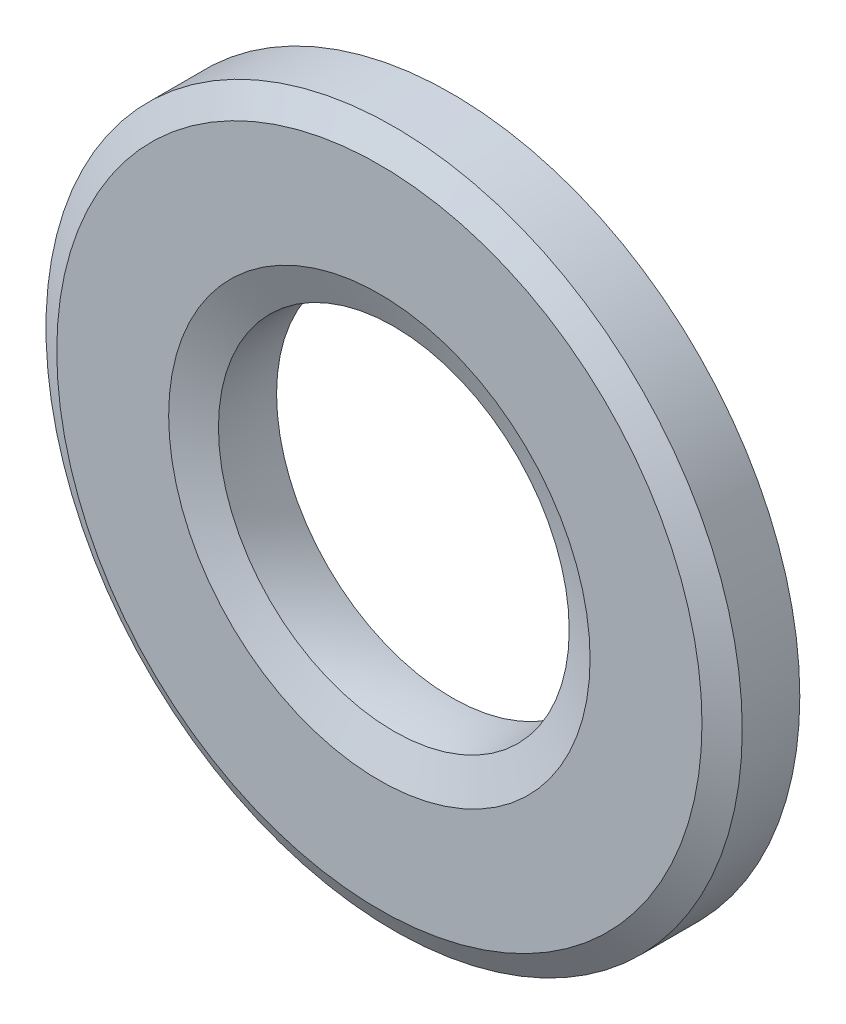
SolidWorks part; units mm, degrees
other "Imported1" parameters "D1"=0.254
ref_plane "Front Plane" through (0, 0, 0) normal (0, 0, 1) x (1, 0, 0)
ref_plane "Top Plane" through (0, 0, 0) normal (0, 1, 0) x (1, 0, 0)
ref_plane "Right Plane" through (0, 0, 0) normal (1, 0, 0) x (0, 0, -1)
sketch "Sketch1" plane through (0, 0, 0) normal (0, 0, 1) x (1, 0, 0)
  line L0 (-6, 0) -> (6, 0) construction
  line L1 (-3, 0) -> (3, 0) construction
  circle A0 centre (0, 0) radius 3 construction
  circle A1 centre (0, 0) radius 6 construction
  point P8 (0, 0)
  point P9 (0, 6)
  point P11 (3, 0)
  dimension "ID" = 6
  dimension "OD" = 12
sketch "Sketch2" plane through (0, 0, 0) normal (1, 0, 0) x (0, 0, -1)
  line L0 (-0.75, 6) -> (0.75, 6) construction
  point P2 (0, 6)
  dimension "Thickness" = 1.5
sketch "Sketch3" plane through (0, 0, 0) normal (0, 0, 1) x (1, 0, 0)
  circle A0 centre (0, 0) radius 3
  circle A1 centre (0, 0) radius 6
extrude "Boss-Extrude1" add sketch "Sketch3" along normal up to vertex (0.75 mm away) and the other way up to vertex (0.75 mm away) up to point (0, 6, 0.75) other way up to point (0, 6, -0.75)
chamfer "Chamfer1" distance 0.254 angle 60 2 edges at (6, 0, -0.75) (6, 0, 0.75)
sketch "Sketch4" plane through (0, 0, 0) normal (1, 0, 0) x (0, 0, -1)
  line L3 (-0.75, 2.9492) -> (-0.75, 3.0508)
  line L4 (-0.75, 2.9492) -> (0.75, 2.9492)
  line L5 (0.75, 2.9492) -> (0.75, 3.0508)
  line L6 (-0.75, 0) -> (0.75, 0) construction
  arc A0 (-0.75, 3.0508) -> (0.75, 3.0508) centre (0, 8.5618) ccw
  point P0 (0, 3)
  point P9 (-0.75, 3)
  point P13 (0, 0)
  dimension "D1" = 0.0508
revolve "Cut-Revolve1" cut sketch "Sketch4" angle 360 about L6
chamfer "Chamfer2" distance 0.254 angle 60 2 edges at (0, -3.0508, -0.75) (0, -3.0508, 0.75)
equation "\"D1@Chamfer2\"=\"D1@Chamfer1\""
